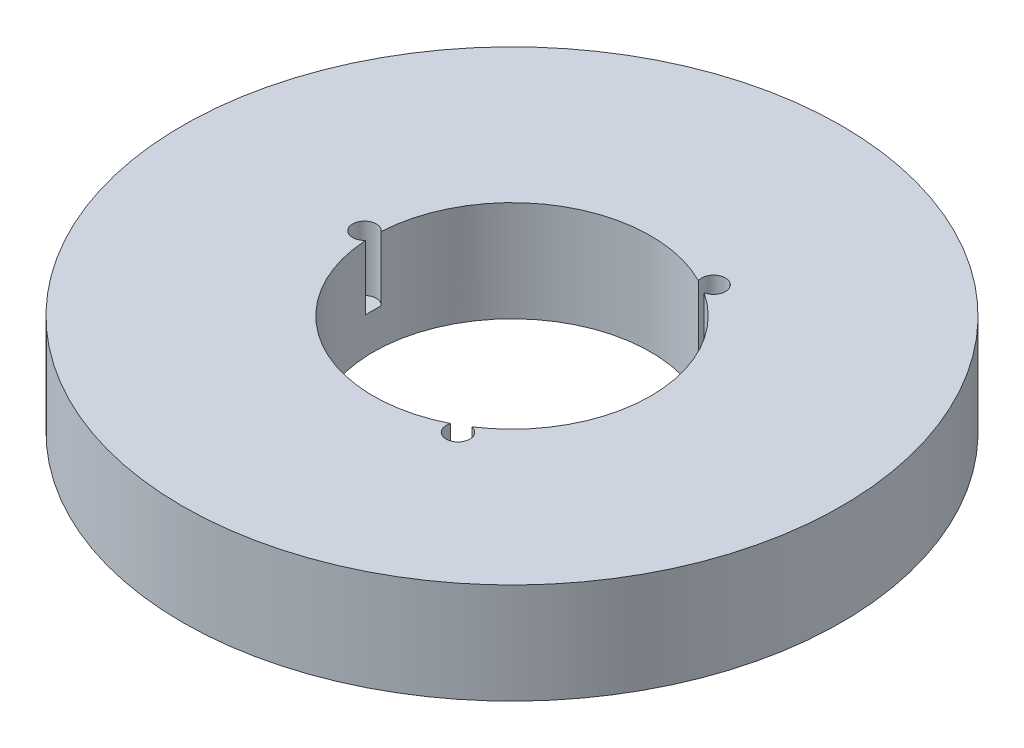
SolidWorks part; units mm, degrees
ref_plane "Front Plane" through (0, 0, 0) normal (0, 0, 1) x (1, 0, 0)
ref_plane "Top Plane" through (0, 0, 0) normal (0, 1, 0) x (1, 0, 0)
ref_plane "Right Plane" through (0, 0, 0) normal (1, 0, 0) x (0, 0, -1)
sketch "Sketch1" plane through (0, 0, 0) normal (0, 1, 0) x (1, 0, 0)
  circle A0 centre (0, 0) radius 95
  dimension "FLANGE_OD" = 190
extrude "Boss-Extrude1" add sketch "Sketch1" along normal blind 29
sketch "Sketch2" plane through (0, 0, 0) normal (0, 1, 0) x (1, 0, 0)
  circle A0 centre (0, 0) radius 40
  dimension "BORE_D" = 80
extrude "Cut-Extrude1" cut sketch "Sketch2" along normal through all
sketch "Sketch3" plane through (0, 29, 0) normal (0, 1, 0) x (1, 0, 0)
  circle A0 centre (0, 0) radius 42.5279 construction
  circle A1 centre (-42.5279, 0) radius 3.4167
  dimension "BOLT_D" = 6.8333
  dimension "BOLT_PCD" = 85.0558
extrude "Cut-Extrude2" cut sketch "Sketch3" against normal blind 18.5806
pattern_circular "CirPattern1" count 3 over 360 about axis through (0, 0, 0) along (0, 1, 0) of "Cut-Extrude2"
